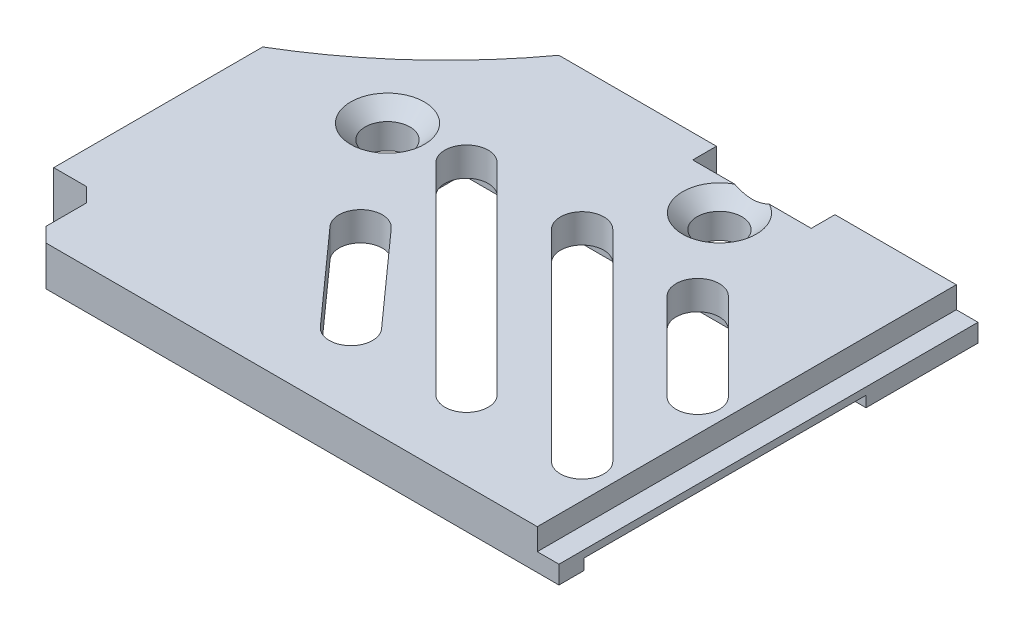
SolidWorks part; units mm, degrees
material "PPS"
ref_plane "前视基准面" through (0, 0, 0) normal (0, 0, 1) x (1, 0, 0)
ref_plane "上视基准面" through (0, 0, 0) normal (0, 1, 0) x (1, 0, 0)
ref_plane "右视基准面" through (0, 0, 0) normal (1, 0, 0) x (0, 0, -1)
sketch "基座草图-前" plane through (0, 0, 0) normal (0, 1, 0) x (1, 0, 0)
  line L2 (-24.7152, 2.0807) -> (-24.5, 0.3125)
  line L6 (-22.5, -14.2499) -> (-22.5, -7.2636)
  line L8 (-22.5, -7.2636) -> (-24.5, -7.2636)
  line L9 (-24.5, -7.2636) -> (-24.5, 0.3125)
  line L10 (-24.5, 0.3125) -> (-25.1116, 5.3379) construction
  line L12 (-26.5, 1.2398) -> (-26.5, -14.2499)
  line L13 (-26.5, -14.2499) -> (-22.5, -14.2499)
  line L16 (-4.1009, 11.812) -> (-4.1009, 8.358) construction
  line L17 (-4.1009, 8.358) -> (4.1009, 8.358)
  line L18 (4.1009, 8.358) -> (4.1009, 11.8106) construction
  line L19 (-16.253, 10) -> (-4.1009, 10)
  line L20 (-4.1009, 10) -> (-4.1009, 8.358)
  line L21 (4.1009, 8.358) -> (4.1009, 10)
  line L22 (0, 0.0001) -> (0, -23.6618) construction
  line L24 (4.1009, 10) -> (12.5, 10)
  line L25 (12.5, 10) -> (12.5, -14.2499)
  line L26 (12.5, -14.2499) -> (-26.5, -14.2499)
  arc A1 (-26.5, 2.4898) -> (-24.8662, 3.3216) centre (-28.6129, 8.6608) ccw construction
  arc A3 (-25.1116, 5.3379) -> (-57.77, 17.2644) centre (-45.4537, 0.3125) ccw construction
  arc A4 (-26.5, 1.2398) -> (-24.7152, 2.0807) centre (-28.3556, 7.493) ccw
  arc A5 (-17.503, 10) -> (-24.8662, 3.3216) centre (-44.5319, 32.4021) cw
  arc A6 (-16.253, 10) -> (-24.7152, 2.0807) centre (-44.1427, 31.321) cw
  circle A7 centre (0, 6.108) radius 1.55
  circle A8 centre (-16.866, 0) radius 1.55
  dimension "D1" = 1.25
  dimension "D2" = 1.25
  dimension "D3" = 1.25
  dimension "D4" = 16.866
  dimension "D5" = 12.5
  dimension "D6" = 9.9999
  dimension "D7" = 14.25
  dimension "D8" = 22.5
  dimension "D9" = 26.5
  dimension "D10" = 24.5
  dimension "D11" = 7.2637
extrude "基座-前" add sketch "基座草图-前" along normal blind 2.75 contours L19 A6 L2 L9 L8 L6 L26 L25 L24 L21 L17 L20 A8 A7 region at (-5.0831, 0, 2.6655)
sketch "基座草图-后" plane through (0, 0, 0) normal (0, 1, 0) x (1, 0, 0)
  line L0 (-22.5, -14.2499) -> (-22.5, -18.9999)
  line L1 (-22.5, -18.9999) -> (12.5, -18.9999)
  line L2 (12.5, -18.9999) -> (12.5, -14.2499)
  line L3 (12.5, 10) -> (12.5, -14.2499) construction
  line L4 (12.5, -14.2499) -> (-22.5, -14.2499) construction
  line L5 (-22.5, -14.2499) -> (12.5, -14.2499)
  dimension "D1" = 4.75
extrude "基座-后" add sketch "基座草图-后" along normal up to surface (2.75 mm away) up to face at (-16.866, 2.75, 1.55)
sketch "卡榫草图" plane through (0, 0, 0) normal (0, 1, 0) x (1, 0, 0)
  line L0 (-24.5, -7.2636) -> (-23.5, -7.2636)
  line L1 (-22.5, -7.2636) -> (-24.5, -7.2636) construction
  line L2 (-23.5, -7.2636) -> (-23.5, -14.2136)
  line L3 (-23.5, -14.2136) -> (-24.5, -14.2136)
  line L6 (-22.5, -18.9999) -> (-22.5, -7.2636) construction
  line L7 (-24.5, -14.2136) -> (-25.75, -14.2136)
  line L8 (-25.75, -14.2136) -> (-25.75, 0.3125)
  line L9 (-25.75, 0.3125) -> (-24.5, 0.3125) construction
  line L11 (-24.5, -7.2636) -> (-24.5, 0.3125) construction
  line L12 (-24.5, -7.2636) -> (-24.5, 0.3125)
  line L13 (-24.5, -7.2636) -> (-24.5, -14.2136)
  line L14 (-23.5, -7.2636) -> (-22.5, -7.2636)
  line L15 (-22.5, -7.2636) -> (-22.5, -14.2136)
  line L16 (-22.5, -14.2136) -> (-23.5, -14.2136)
  line L17 (-25.75, 0.3125) -> (-26.2135, 4.1214) construction
  line L18 (-24.7152, 2.0807) -> (-24.5, 0.3125) construction
  line L19 (-25.8753, 1.3423) -> (-25.75, 0.3125)
  line L20 (-24.7152, 2.0807) -> (-24.5, 0.3125)
  arc A0 (-24.7152, 2.0807) -> (-25.8753, 1.3423) centre (-44.1427, 31.321) cw
  arc A1 (-24.7152, 2.0807) -> (-16.253, 10) centre (-44.1427, 31.321) ccw construction
  dimension "D1" = 1
  dimension "D2" = 1.25
  dimension "D3" = 6.95
extrude "卡榫结构-1" add sketch "卡榫草图" along normal up to surface (2.75 mm away) contours L13 L12 L9 L8 L7 | L0 L13 L3 L2 | L12 L0 | L16 L15 L14 L2 region at (-25.1278, 0, 6.2521) region at (-24, 0, 10.7386) region at (-23, 0, 10.7386) up to face at (-16.866, 2.75, 1.55)
extrude "卡榫结构-2-注意PCB凸出部分" add sketch "草图5<4>" against normal blind 4 from surface contours L0 L13 L3 L2 | L13 L12 L9 L8 L7 region at (-25.1278, 0, 6.2521) region at (-24, 0, 10.7386) starting at face at (-9.4355, 0, 0.7086)
sketch "草图5<4>" plane through (0, 0, 0) normal (0, 1, 0) x (1, 0, 0) same geometry as "卡榫草图"
sketch "卡榫限位" plane through (0, 0, 0) normal (0, 1, 0) x (1, 0, 0)
  line L0 (12.5, 10) -> (14, 10)
  line L1 (14, 10) -> (14, -18.9999)
  line L2 (14, -18.9999) -> (12.5, -18.9999)
  line L3 (12.5, -18.9999) -> (12.5, 10)
  dimension "D1" = 1.5
extrude "限位结构" add sketch "卡榫限位" along normal blind 1.25
sketch "散热口位置" plane through (0, 0, 0) normal (0, 1, 0) x (1, 0, 0)
  line L0 (-13.916, -17.25) -> (-13.916, 2.25)
  line L1 (14, -18.9999) -> (14, 10) construction
  line L2 (-13.916, 2.25) -> (14, 2.25)
  line L4 (14, 2.25) -> (14, -17.25)
  line L5 (14, -17.25) -> (-13.916, -17.25)
  circle A0 centre (-16.866, 0) radius 1.55 construction
  dimension "D1" = 2.25
  dimension "D2" = 2.95
  dimension "D3" = 19.5
extrude "稳压PCB器件高度补偿" cut sketch "散热口位置" along normal blind 0.75
sketch "散热" plane through (0, 0.75, 0) normal (0, -1, 0) x (1, 0, 0)
  line L0 (0, 0) -> (24.2492, 0) construction
  line L1 (4.2339, -0.37) -> (10.2676, 5.6638) construction
  line L2 (3.1732, 0.6907) -> (9.2069, 6.7244)
  line L3 (5.2945, -1.4307) -> (11.3283, 4.6031)
  line L4 (-3.7661, -0.37) -> (10.1432, 13.5393) construction
  line L5 (-4.8268, 0.6907) -> (9.0825, 14.6)
  line L6 (-2.7055, -1.4307) -> (11.2038, 12.4787)
  line L7 (-11.7661, -0.37) -> (2.1432, 13.5393) construction
  line L8 (-12.8268, 0.6907) -> (1.0825, 14.6)
  line L9 (-10.7055, -1.4307) -> (3.2038, 12.4787)
  line L10 (4.2339, -0.37) -> (-3.7661, -0.37) construction
  line L11 (-3.7661, -0.37) -> (-11.7661, -0.37) construction
  line L12 (-5.8568, 13.5393) -> (-11.5554, 7.1695) construction
  line L13 (-4.7389, 12.5392) -> (-10.4375, 6.1694)
  line L14 (-6.9748, 14.5394) -> (-12.6734, 8.1696)
  line L15 (-5.8568, 13.5393) -> (2.1432, 13.5393) construction
  arc A0 (3.1732, 0.6907) -> (5.2945, -1.4307) centre (4.2339, -0.37) ccw
  arc A1 (11.3283, 4.6031) -> (9.2069, 6.7244) centre (10.2676, 5.6638) ccw
  arc A2 (-4.8268, 0.6907) -> (-2.7055, -1.4307) centre (-3.7661, -0.37) ccw
  arc A3 (11.2038, 12.4787) -> (9.0825, 14.6) centre (10.1432, 13.5393) ccw
  arc A4 (-12.8268, 0.6907) -> (-10.7055, -1.4307) centre (-11.7661, -0.37) ccw
  arc A5 (3.2038, 12.4787) -> (1.0825, 14.6) centre (2.1432, 13.5393) ccw
  arc A6 (-4.7389, 12.5392) -> (-6.9748, 14.5394) centre (-5.8568, 13.5393) ccw
  arc A7 (-12.6734, 8.1696) -> (-10.4375, 6.1694) centre (-11.5554, 7.1695) ccw
  point P5 (7.2507, 2.6469)
  point P14 (3.1885, 6.5847)
  point P20 (-4.8115, 6.5847)
  point P26 (-8.7061, 10.3544)
  dimension "D1" = 135
  dimension "D2" = 3
  dimension "D3" = 8
extrude "切除-拉伸2" cut sketch "散热" against normal through all
chamfer "倒角1" distance 1 angle 45 3 edges at (-20.6617, 2.75, -5.2238) (-22.5, 1.375, 18.9999) (-22.5, 1.375, 14.2136)
chamfer "倒角2" distance 1 angle 45 2 edges at (-16.866, 2.75, 1.55) (0, 2.75, -4.558)
sketch "草图1" plane through (0, -4, 0) normal (0, -1, 0) x (1, 0, 0)
  line L0 (-24.7152, -2.0807) -> (-24.5, -0.3125)
  line L1 (-24.5, -0.3125) -> (-24.5, 7.2636)
  line L2 (-24.5, 7.2636) -> (-23.5, 7.2636)
  line L3 (-23.5, 7.2636) -> (-23.5, 7.5136)
  line L4 (-23.5, 14.2136) -> (-23.5, 7.2636) construction
  line L5 (-23.5, 7.5136) -> (-24.75, 7.5136)
  line L8 (-24.9466, -1.9283) -> (-24.75, -0.3125)
  line L9 (-24.75, -0.3125) -> (-24.75, 7.5136)
  arc A0 (-24.7152, -2.0807) -> (-25.8753, -1.3423) centre (-44.1427, -31.321) ccw construction
  arc A1 (-24.9466, -1.9283) -> (-24.7152, -2.0807) centre (-44.1427, -31.321) cw
  point P18 (-24, 7.2636)
  dimension "D1" = 0.25
  dimension "D2" = 0.2482
  dimension "D3" = 0.25
extrude "公差切除" cut sketch "草图1" against normal up to surface (4 mm away) from surface up to face at (0, 0, -4.558) starting at face at (-24.7609, -4, 4.864)
